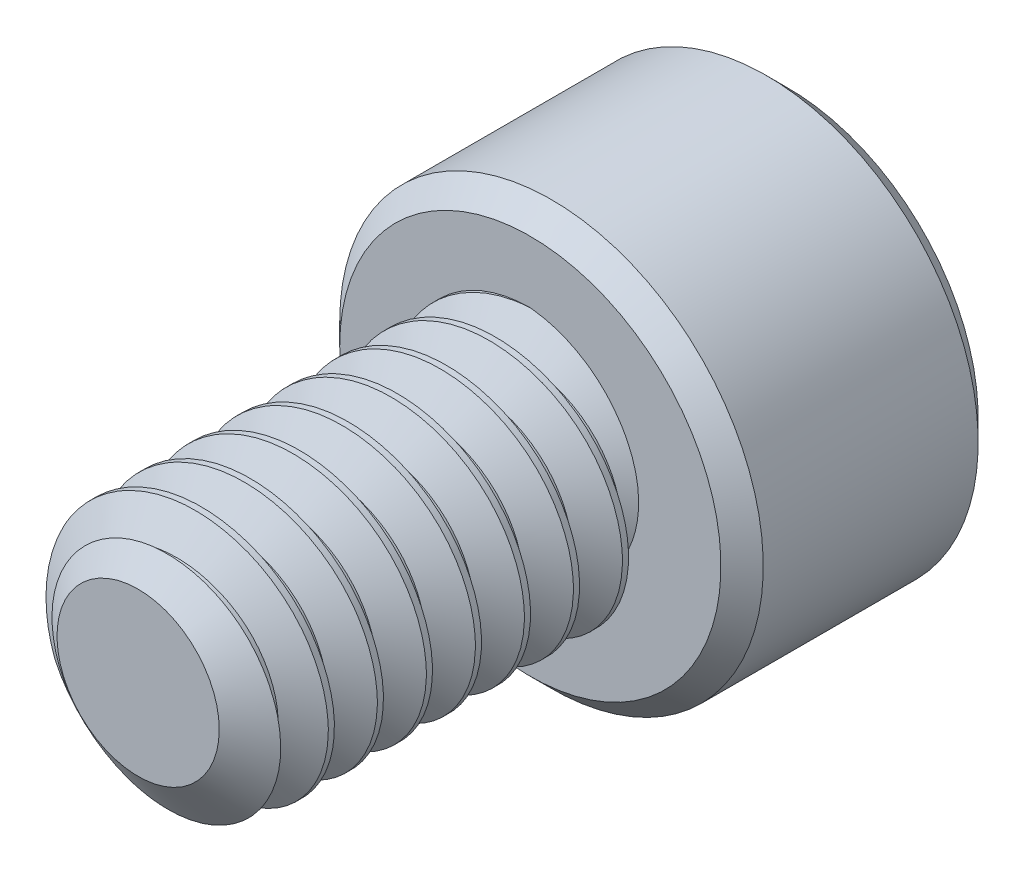
SolidWorks part; units mm, degrees
ref_plane "Front Plane" through (0, 0, 0) normal (0, 0, 1) x (1, 0, 0)
ref_plane "Top Plane" through (0, 0, 0) normal (0, 1, 0) x (1, 0, 0)
ref_plane "Right Plane" through (0, 0, 0) normal (1, 0, 0) x (0, 0, -1)
sketch "Sketch1" plane through (0, 0, 0) normal (0, 0, 1) x (1, 0, 0)
  circle A0 centre (0, 0) radius 2.0828
  dimension "OD" = 4.1656
extrude "Extrude1" add sketch "Sketch1" against normal blind 6.35
sketch "Sketch2" plane through (0, 0, 0) normal (0, 0, 1) x (1, 0, 0)
  circle A0 centre (0, 0) radius 2.0828 construction
  circle A1 centre (0, 0) radius 2.0828
curve "Helix/Spiral1" pitch 0.7937 height 7.1437 turns 9 parameters "pitch"=0.7937
sketch "Sketch3" plane through (0, 0, 0) normal (1, 0, 0) x (0, 0, -1)
  line L0 (-0.6945, 2.0828) -> (-0.3969, 1.5672)
  line L1 (-0.3969, 1.5672) -> (-0.2977, 1.5672)
  line L2 (-0.2977, 1.5672) -> (0, 2.0828)
  line L3 (-0.6945, 2.0828) -> (0, 2.0828)
  line L4 (-0.3473, 2.0828) -> (-0.3473, 1.5672) construction
  line L5 (-0.5457, 1.825) -> (-0.1488, 1.825) construction
  line L6 (0, 2.0828) -> (0, -2.0828) construction
  dimension "D1" = 0.0992
  dimension "D2" = 0.3969
  dimension "D3" = 60
sweep "Cut-Sweep1" cut profiles "Sketch3" path "Helix/Spiral1"
sketch "Sketch4" plane through (0, 0, 0) normal (1, 0, 0) x (0, 0, -1)
  line L0 (0.5388, 2.0828) -> (0, 1.3132)
  line L1 (0, 1.3132) -> (0, 2.0828)
  line L2 (0.5388, 2.0828) -> (0, 2.0828)
  line L3 (-0.6945, 2.0828) -> (0, 2.0828) construction
  line L4 (0, 0) -> (7.0209, 0) construction
  dimension "D1" = 55
  dimension "D2" = 0.254
revolve "Cut-Revolve1" cut sketch "Sketch4" angle 360 about L4
sketch "Sketch5" plane through (0, 0, 0) normal (1, 0, 0) x (0, 0, -1)
  line L0 (6.35, -1.5805) -> (6.35, 1.4861) construction
  line L1 (6.35, 2.2098) -> (15.9635, 2.2098)
  line L2 (6.35, 2.2098) -> (6.35, 0)
  line L3 (6.35, 0) -> (15.875, 0)
  line L4 (15.875, 1.8796) -> (15.875, 0)
  line L5 (15.9635, 2.2098) -> (15.875, 1.8796)
  line L6 (0, 0) -> (9.9695, 0) construction
  point P3 (15.875, 2.2098)
  point P10 (15.875, 2.2098)
  dimension "D1" = 0.3302
  dimension "Thread min" = 15.875
  dimension "D2" = 0.127
  dimension "D3" = 15
revolve "partially thread" [suppressed] add sketch "Sketch5" angle 360 about L6
sketch "Sketch6" plane through (0, 0, -6.35) normal (0, 0, -1) x (-1, 0, 0)
  circle A0 centre (0, 0) radius 3.429
  dimension "head dia" = 6.858
extrude "Extrude2" add sketch "Sketch6" along normal blind 4.1656
sketch "Sketch7" plane through (0, 0, -10.5156) normal (0, 0, -1) x (-1, 0, 0)
  line L1 (0, 2.0622) -> (-1.7859, 1.0311)
  line L2 (-1.7859, 1.0311) -> (-1.7859, -1.0311)
  line L3 (-1.7859, -1.0311) -> (0, -2.0622)
  line L4 (0, -2.0622) -> (1.7859, -1.0311)
  line L5 (1.7859, -1.0311) -> (1.7859, 1.0311)
  line L6 (1.7859, 1.0311) -> (0, 2.0622)
  circle A0 centre (0, 0) radius 1.7859 construction
  dimension "hex dia" = 3.5719
extrude "Cut-Extrude1" cut sketch "Sketch7" against normal blind 2.6789
sketch "Sketch8" plane through (0, 0, -10.5156) normal (0, 0, -1) x (-1, 0, 0)
  circle A0 centre (0, 0) radius 2.0622
extrude "Cut-Extrude2" cut sketch "Sketch8" against normal through all draft 45
chamfer "Chamfer1" distance 0.3429 angle 45 2 edges at (-3.429, 0, -10.5156) (-3.429, 0, -6.35)
sketch "Sketch9" plane through (0, 0, 0) normal (1, 0, 0) x (0, 0, -1)
  line L0 (0, 2.0828) -> (0, -2.0828) construction
  line L1 (8.3344, 2.0828) -> (8.3344, -2.0828) construction
  dimension "D1" = 8.3344
equation "\"D3@Helix/Spiral1\" = \"screw length@Extrude1\"+\"pitch@Helix/Spiral1\""
equation "\"D1@Sketch3\" = \"pitch@Helix/Spiral1\"*.125"
equation "\"D2@Sketch3\" = \"pitch@Helix/Spiral1\"*.5"
equation "\"D1@Cut-Extrude1\" = \"hex dia@Sketch7\"*.75"
equation "\"D1@Chamfer1\" = \"head dia@Sketch6\"*.05"
equation "\"D1@Sketch9\" = \"pitch@Helix/Spiral1\"*10.5"
